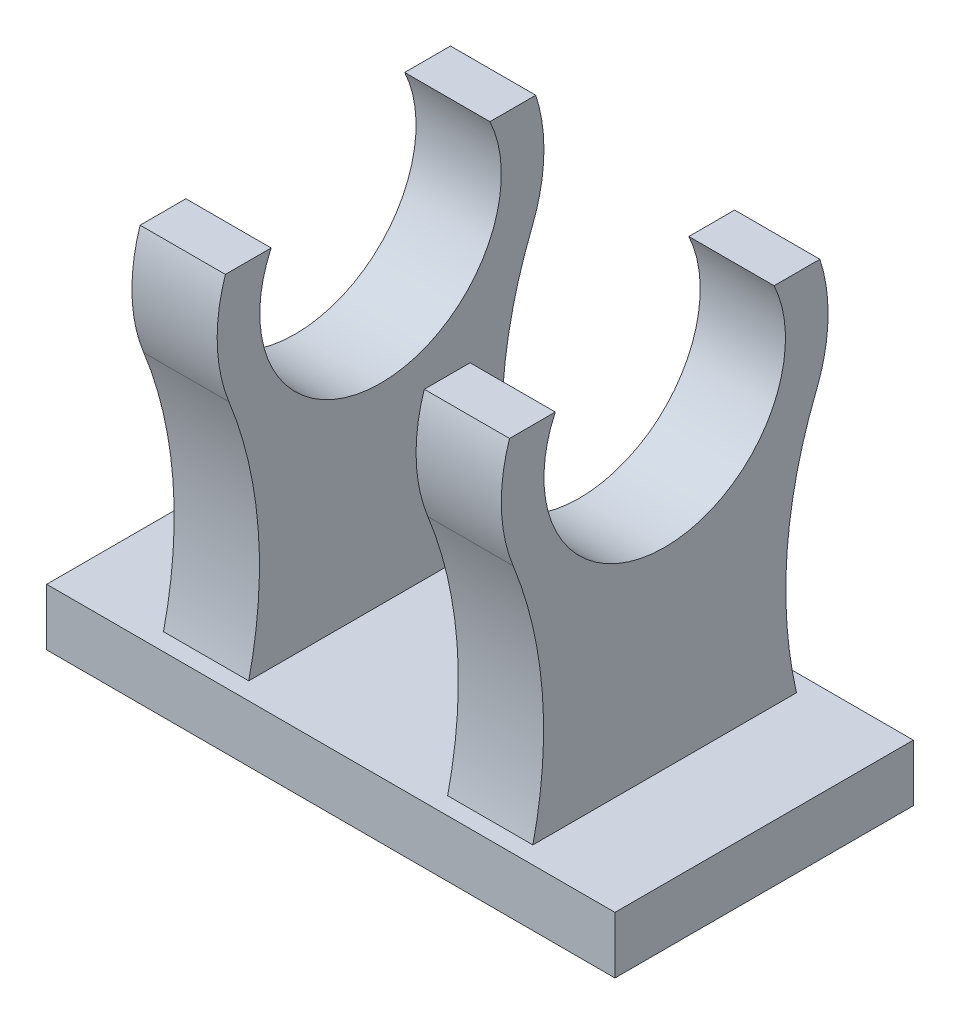
SolidWorks part; units mm, degrees
ref_plane "Front Plane" through (0, 0, 0) normal (0, 0, 1) x (1, 0, 0)
ref_plane "Top Plane" through (0, 0, 0) normal (0, 1, 0) x (1, 0, 0)
ref_plane "Right Plane" through (0, 0, 0) normal (1, 0, 0) x (0, 0, -1)
sketch "Sketch1" plane through (0, 0, 0) normal (1, 0, 0) x (0, 0, -1)
  line L1 (-5.461, 14.8) -> (-3.85, 14.8)
  line L2 (-5.25, 0) -> (5.25, 0)
  line L4 (-5.5267, 14.5868) -> (5.25, 0) construction
  line L5 (-5.25, 0) -> (5.5267, 14.5868) construction
  line L6 (3.85, 14.8) -> (5.461, 14.8)
  line L7 (0, 0) -> (0, 13) construction
  arc A0 (-3.85, 14.8) -> (3.85, 14.8) centre (0, 13) ccw
  arc A1 (-5.461, 14.8) -> (-5.3341, 10.8528) centre (0, 13) ccw
  arc A2 (-5.25, 0) -> (-5.3341, 10.8528) centre (-19.0797, 5.3196) ccw
  arc A3 (5.25, 0) -> (5.3341, 10.8528) centre (19.0797, 5.3196) cw
  arc A4 (5.3341, 10.8528) -> (5.461, 14.8) centre (0, 13) ccw
  point P1 (0, 7.1061)
  point P16 (0, 12.7071)
  point P18 (0, 16.4747)
  dimension "D2" = 8.5
  dimension "D1" = 1.5
  dimension "D3" = 1.8
  dimension "D4" = 13
extrude "Boss-Extrude1" add sketch "Sketch1" along normal blind 1.5 and the other way blind 1.5
sketch "Sketch3" plane through (0, 0, 0) normal (0, -1, 0) x (1, 0, 0)
  line L0 (5, -5.25) -> (5, 5.25)
  line L1 (5, -5.25) -> (-5, -5.25)
  line L2 (5, 5.25) -> (-5, 5.25)
  line L3 (-5, -5.25) -> (-5, 5.25)
  line L4 (5, -5.25) -> (-5, 5.25) construction
  line L5 (5, 5.25) -> (-5, -5.25) construction
  point P1 (0, 0)
  dimension "D1" = 10
extrude "Boss-Extrude2" add sketch "Sketch3" against normal blind 2
mirror "Mirror1" about plane through (5, 2, -5.25) normal (1, 0, 0) of bodies 102
